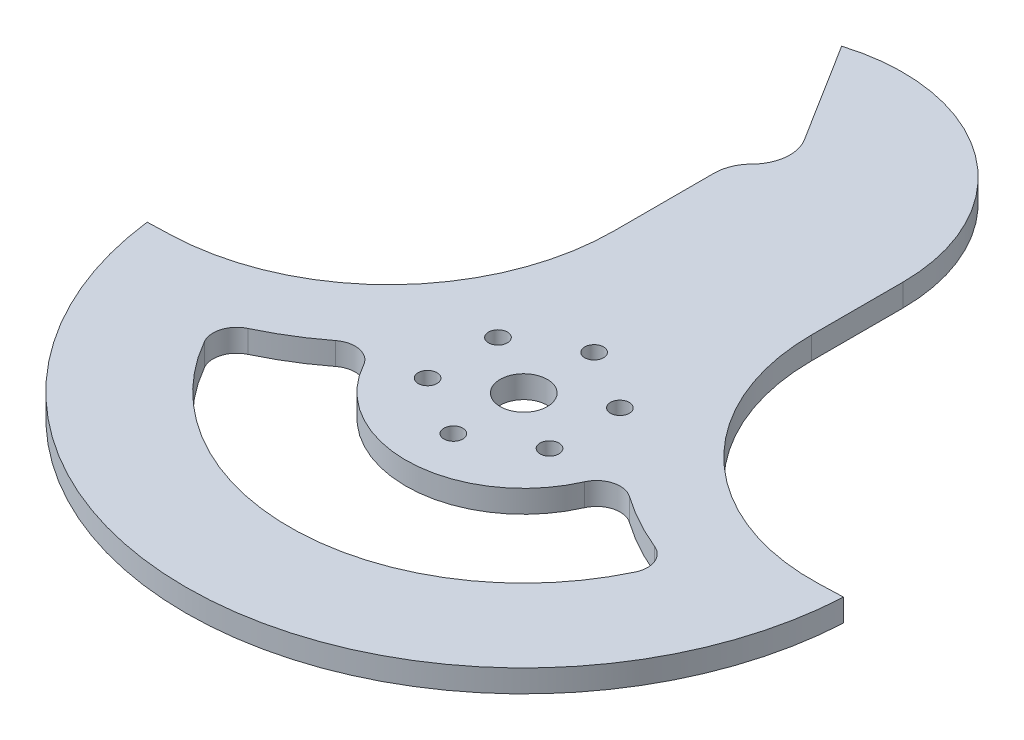
SolidWorks part; units mm, degrees
ref_plane "Front Plane" through (0, 0, 0) normal (0, 0, 1) x (1, 0, 0)
ref_plane "Top Plane" through (0, 0, 0) normal (0, 1, 0) x (1, 0, 0)
ref_plane "Right Plane" through (0, 0, 0) normal (1, 0, 0) x (0, 0, -1)
other "Center of Mass"
sketch "Sketch1" plane through (0, 0, 0) normal (0, 1, 0) x (1, 0, 0)
  line L0 (0, 0) -> (-23040.0357, 36803.9862) construction
  line L1 (0, -1000) -> (0, 49000) construction
  line L2 (-29.7853, 97.136) -> (-16.5198, 75.9457)
  line L3 (18.7342, 112.0138) -> (41531.855, 12841.4067) construction
  line L4 (-20, 60.3286) -> (20, 60.3286) construction
  line L5 (-20, 60.3286) -> (-20, 39.1549)
  line L6 (20, 60.3286) -> (20, 40.9875)
  line L7 (0, 0) -> (-71.0663, -8.7258) construction
  line L8 (0, 0) -> (71.5019, -3.7473) construction
  line L9 (-71.0663, -8.7258) -> (71.5019, -3.7473) construction
  line L10 (-71.0663, -8.7258) -> (-66.0694, -8.5513)
  line L11 (71.5019, -3.7473) -> (66.5049, -3.9218)
  line L12 (-28.8426, 54.8122) -> (35326.4965, 35410.1512) construction
  circle A0 centre (0, 0) radius 101.6 construction
  arc A1 (-16.5198, 75.9457) -> (-17.6481, 66.0067) centre (-23.3262, 71.6848) cw
  arc A2 (-17.6481, 66.0067) -> (-20, 60.3286) centre (-11.97, 60.3286) ccw
  arc A3 (-29.7853, 97.136) -> (20, 60.3286) centre (-18.4989, 60.3286) cw
  circle A4 centre (0, 0) radius 71.6 construction
  arc A5 (-71.0663, -8.7258) -> (71.5019, -3.7473) centre (0, 0) ccw
  arc A6 (-66.0694, -8.5513) -> (-20, 39.1549) centre (-67.7353, 39.1549) ccw
  arc A7 (20, 40.9875) -> (66.5049, -3.9218) centre (64.9367, 40.9875) ccw
  circle A8 centre (0, 0) radius 30.5026 construction
  point P9 (0, 60.3286)
  point P20 (0, -71.6)
  point P21 (0, -101.6)
  point P31 (2.4988, -71.5564)
  point P34 (-15.2961, 71.6848)
  dimension "D1" = 203.2
  dimension "D2" = 75
  dimension "D3" = 25
  dimension "D4" = 40
  dimension "D5" = 30
  dimension "D6" = 92
  dimension "D7" = 170
  dimension "D8" = 5
  dimension "D9" = 45
extrude "Boss-Extrude1" add sketch "Sketch1" along normal blind 4.7625
sketch "Sketch6" plane through (0, 4.7625, 0) normal (0, 1, 0) x (1, 0, 0)
  line L0 (-41.0794, -17.6358) -> (-47.4528, -4.0572) construction
  line L1 (29.2213, -7.1458) -> (38.1596, 4.9002) construction
  arc A0 (-45.5884, -19.5412) -> (46.8909, -16.168) centre (0, 0) ccw
  arc A1 (-16.623, 2.7783) -> (-45.5884, -19.5412) centre (-67.7353, 39.1549) cw
  arc A2 (14.252, 8.9958) -> (46.8909, -16.168) centre (64.9367, 40.9875) ccw
  arc A3 (-16.623, 2.7783) -> (14.252, 8.9958) centre (0, 0) ccw
  arc A4 (-66.0694, -8.5513) -> (-20, 39.1549) centre (-67.7353, 39.1549) ccw construction
  arc A5 (-71.0663, -8.7258) -> (71.5019, -3.7473) centre (0, 0) ccw construction
  arc A6 (20, 40.9875) -> (66.5049, -3.9218) centre (64.9367, 40.9875) ccw construction
  circle A7 centre (0, 0) radius 30.5026 construction
  point P23 (0, -49.6)
  point P24 (27.5979, 7.7355)
  point P26 (-27.0864, -6.2166)
  point P27 (23.3858, 11.7369)
  dimension "D1" = 22
  dimension "D2" = 15
extrude "Cut-Extrude2" cut sketch "Sketch6" against normal through all
fillet "Fillet6" radius 5 2 edges at (46.8909, 2.3813, 16.168) (-45.5884, 2.3813, 19.5412)
sketch "Sketch7" plane through (0, 4.7625, 0) normal (0, 1, 0) x (1, 0, 0)
  circle A0 centre (0, 0) radius 25
  point P3 (0, 0)
  dimension "D1" = 50
extrude "Boss-Extrude5" add sketch "Sketch7" against normal up to surface (4.7625 mm away) up to face at (0.9289, 0, 19.6333)
fillet "Fillet7" radius 5 2 edges at (24.7558, 2.3813, 3.486) (-24.2527, 2.3813, 6.0666)
sketch "Sketch8" plane through (0, 4.7625, 0) normal (0, 1, 0) x (1, 0, 0)
  circle A0 centre (0.1682, -0.1726) radius 5
  point P2 (1.1861, -0.8784)
  point P3 (0.208, -0.178)
  point P4 (0.1725, -0.2345)
  point P5 (0, 0)
  point P6 (0.1672, -0.1743)
  point P7 (0.1681, -0.1726)
  point P8 (0.1682, -0.1726)
  point P9 (0, 0)
  point P10 (0, 0)
  dimension "D1" = 10
extrude "Cut-Extrude3" cut sketch "Sketch8" against normal through all
sketch "Sketch10" plane through (0, 4.7625, 0) normal (0, 1, 0) x (1, 0, 0)
  circle A0 centre (0.1682, -15.0858) radius 9.9133 construction
  circle A1 centre (0, 0) radius 25 construction
  circle A2 centre (0.1682, -0.1726) radius 5 construction
  circle A3 centre (0.1682, -15.0858) radius 2
  circle A4 centre (-12.7471, -7.6292) radius 2
  circle A5 centre (-12.7471, 7.2841) radius 2
  circle A6 centre (0.1682, 14.7407) radius 2
  circle A7 centre (13.0834, 7.2841) radius 2
  circle A8 centre (13.0834, -7.6292) radius 2
  point P7 (14.4943, 6.8619)
  point P9 (0, 0)
  point P21 (0.1682, -0.1726)
  dimension "D1" = 4
  dimension "D2" = 6
extrude "Cut-Extrude4" cut sketch "Sketch10" against normal through all
